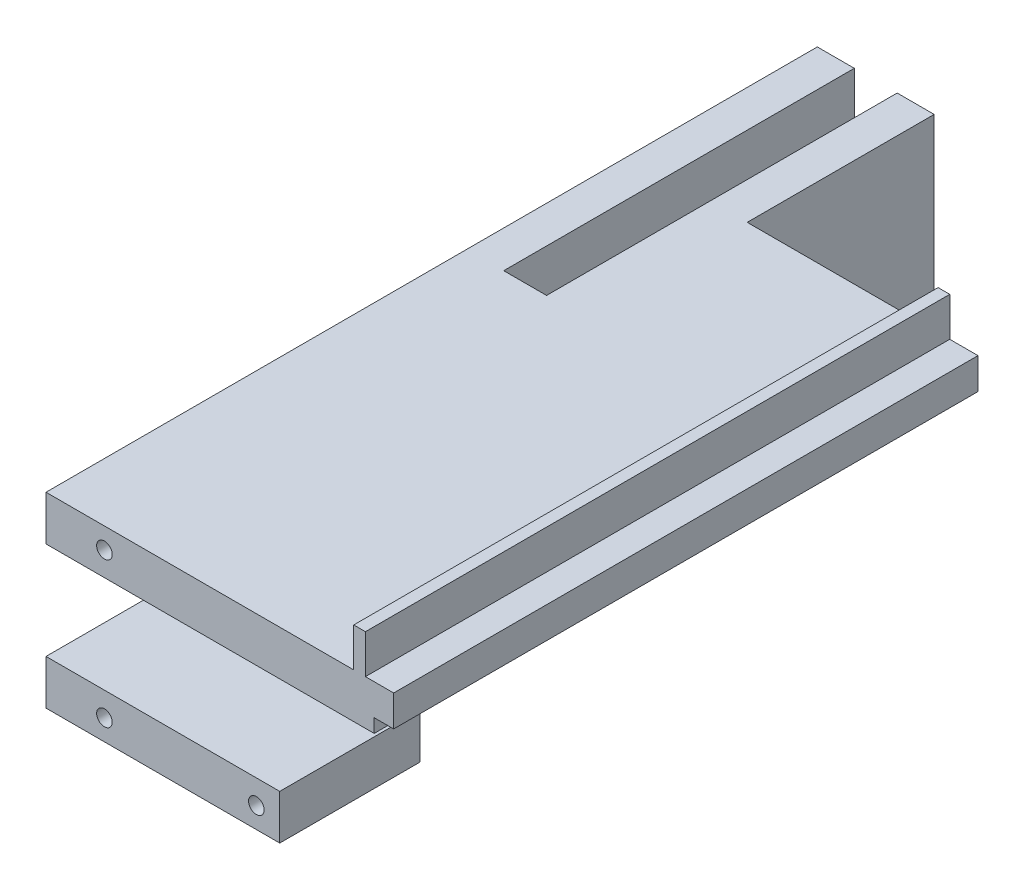
SolidWorks part; units mm, degrees
ref_plane "Alzado" through (0, 0, 0) normal (0, 0, 1) x (1, 0, 0)
ref_plane "Planta" through (0, 0, 0) normal (0, 1, 0) x (1, 0, 0)
ref_plane "Vista lateral" through (0, 0, 0) normal (1, 0, 0) x (0, 0, -1)
sketch "Croquis1" plane through (0, 0, 0) normal (0, 0, 1) x (1, 0, 0)
  line L1 (-66.2162, 31.0113) -> (-6.2162, 31.0113)
  line L2 (-66.2162, 31.0113) -> (-66.2162, -16.9887)
  line L3 (-66.2162, -16.9887) -> (-6.2162, -16.9887)
  line L4 (-6.2162, 31.0113) -> (-6.2162, -16.9887)
  dimension "D1" = 48
  dimension "D2" = 60
extrude "Saliente-Extruir1" add sketch "Croquis1" along normal blind 6
sketch "Croquis4" plane through (0, 0, 6) normal (0, 0, 1) x (1, 0, 0)
  line L0 (-66.2162, 31.0113) -> (-66.2162, 19.5113)
  line L1 (-66.2162, 31.0113) -> (-66.2162, -16.9887) construction
  line L3 (-66.2162, -5.4887) -> (-66.2162, -16.9887)
  line L4 (-66.2162, 31.0113) -> (-6.2162, 31.0113)
  line L6 (-6.2162, 31.0113) -> (-6.2162, 19.5113)
  line L7 (-6.2162, -16.9887) -> (-6.2162, 31.0113) construction
  line L8 (-6.2162, 19.5113) -> (-66.2162, 19.5113)
  line L9 (-66.2162, -5.4887) -> (-6.2162, -5.4887)
  line L10 (-6.2162, -5.4887) -> (-6.2162, -16.9887)
  line L11 (-6.2162, -16.9887) -> (-66.2162, -16.9887)
  dimension "D1" = 25
extrude "Saliente-Extruir3" add sketch "Croquis4" along normal blind 30
sketch "Croquis3" plane through (0, 0, 6) normal (0, 0, 1) x (1, 0, 0)
  circle A0 centre (-51.2162, 25.6613) radius 2.125
  circle A1 centre (-12.2162, 25.6613) radius 2.125
  circle A2 centre (-12.2162, -11.6387) radius 2.125
  circle A3 centre (-51.2162, -11.6387) radius 2.125
  dimension "D7" = 4.25
  dimension "D9" = 4.25
  dimension "D10" = 4.25
  dimension "D2" = 4.25
  dimension "D3" = 37.3
  dimension "D4" = 39
sketch "Croquis5" plane through (0, 0, 36) normal (0, 0, 1) x (1, 0, 0)
  circle A0 centre (-51.2162, 25.6613) radius 2
  circle A1 centre (-12.2162, 25.6613) radius 2
  circle A2 centre (-12.2162, -11.6387) radius 2
  circle A3 centre (-51.2162, -11.6387) radius 2
  dimension "D1" = 4
  dimension "D2" = 4
  dimension "D3" = 4
  dimension "D4" = 4
extrude "Cortar-Extruir3" cut sketch "Croquis5" against normal blind 16
sketch "Croquis6" plane through (0, 0, 0) normal (0, 0, -1) x (-1, 0, 0)
  line L0 (66.2162, -16.9887) -> (6.2162, -16.9887) construction
  line L1 (66.2162, 31.0113) -> (36.2162, 31.0113)
  line L2 (66.2162, 31.0113) -> (66.2162, -16.9887)
  line L3 (66.2162, -16.9887) -> (36.2162, -16.9887)
  line L4 (36.2162, 31.0113) -> (36.2162, -16.9887)
  dimension "D1" = 30
extrude "Saliente-Extruir4" add sketch "Croquis6" along normal blind 162
sketch "Croquis7" plane through (0, 0, -162) normal (0, 0, -1) x (-1, 0, 0)
  circle A0 centre (51.2162, 7.0113) radius 2
  dimension "D1" = 4
extrude "Cortar-Extruir4" cut sketch "Croquis7" against normal blind 16
sketch "Croquis8" plane through (0, 0, -162) normal (0, 0, -1) x (-1, 0, 0)
  line L0 (41.2162, 12.0113) -> (41.2162, 9.5131)
  line L10 (36.2162, 12.0113) -> (41.2162, 12.0113)
  line L11 (36.2162, 12.0113) -> (36.2162, 2.0113)
  line L12 (36.2162, 2.0113) -> (41.2162, 2.0113)
  line L21 (41.2162, 9.5131) -> (44.2162, 9.5131)
  line L23 (41.2162, 4.5131) -> (44.2162, 4.5131)
  line L24 (44.2162, 9.5131) -> (44.2162, 4.5131)
  line L25 (41.2162, 2.0113) -> (41.2162, 4.5131)
  dimension "D1" = 5
  dimension "D2" = 3
  dimension "D3" = 5
sketch "Croquis11" plane through (-36.2162, 0, 0) normal (1, 0, 0) x (0, 0, -1)
  line L1 (-36, 19.5113) -> (-36, 31.0113) construction
  line L4 (-36, 19.5113) -> (-36, 31.0113)
  line L6 (-36, 19.5113) -> (114, 19.5113)
  line L7 (114, 19.5113) -> (114, 31.0113)
  line L8 (162, 31.0113) -> (0, 31.0113) construction
  line L9 (162, 31.0113) -> (0, 31.0113) construction
  line L10 (-36, 31.0113) -> (114, 31.0113)
  dimension "D1" = 150
extrude "Saliente-Extruir6" add sketch "Croquis11" along normal blind 59.25
sketch "Croquis12" plane through (0, 31.0113, 0) normal (0, 1, 0) x (1, 0, 0)
  line L0 (23.0338, -36) -> (-66.2162, -36) construction
  line L1 (15.7838, -36) -> (12.7838, -36)
  line L2 (-66.2162, -36) -> (-66.2162, 162) construction
  line L3 (-66.2162, -36) -> (-66.2162, 162) construction
  line L4 (15.7838, -36) -> (15.7838, 114)
  line L5 (15.7838, 114) -> (12.7838, 114)
  line L6 (23.0338, 114) -> (-36.2162, 114) construction
  line L7 (12.7838, 114) -> (12.7838, -36)
  dimension "D1" = 82
  dimension "D2" = 150
  dimension "D3" = 3
extrude "Saliente-Extruir7" add sketch "Croquis12" along normal blind 10
sketch "Croquis14" plane through (0, 0, -114) normal (0, 0, -1) x (-1, 0, 0)
  line L0 (-23.0338, 23.0113) -> (-18.0338, 23.0113)
  line L1 (-18.0338, 23.0113) -> (-18.0338, 19.5113)
  line L2 (-23.0338, 23.0113) -> (-23.0338, 19.5113)
  line L3 (-23.0338, 19.5113) -> (-18.0338, 19.5113)
  line L4 (36.2162, 19.5113) -> (36.2162, 31.0113)
  line L5 (36.2162, 31.0113) -> (-12.7838, 31.0113)
  line L6 (-23.0338, 31.0113) -> (-23.0338, 19.5113)
  line L7 (-23.0338, 19.5113) -> (36.2162, 19.5113)
  line L8 (36.2162, 19.5113) -> (36.2162, 31.0113) construction
  line L9 (36.2162, 31.0113) -> (-12.7838, 31.0113) construction
  line L10 (-23.0338, 31.0113) -> (-23.0338, 19.5113) construction
  line L11 (-23.0338, 19.5113) -> (36.2162, 19.5113) construction
  line L20 (-12.7838, 31.0113) -> (-12.7838, 41.0113)
  line L22 (-12.7838, 41.0113) -> (-15.7838, 41.0113)
  line L24 (-15.7838, 41.0113) -> (-15.7838, 31.0113)
  line L26 (-15.7838, 31.0113) -> (-23.0338, 31.0113)
  line L27 (-15.7838, 31.0113) -> (-23.0338, 31.0113) construction
  dimension "D2" = 5
  dimension "D3" = 8
  dimension "D1" = 0
extrude "Cortar-Extruir6" cut sketch "Croquis14" against normal through all both and the other way through all
sketch "Croquis15" plane through (0, 0, -162) normal (0, 0, -1) x (-1, 0, 0)
  line L0 (51.2162, 45.0729) -> (51.2162, 16.9496) construction
  line L1 (56.7162, 20.0113) -> (45.7162, 20.0113)
  line L2 (45.7162, 20.0113) -> (45.7162, 31.0113)
  line L3 (56.7162, 20.0113) -> (56.7162, 31.0113)
  line L4 (66.2162, -16.9887) -> (66.2162, 31.0113)
  line L5 (66.2162, 31.0113) -> (36.2162, 31.0113)
  line L6 (36.2162, 31.0113) -> (36.2162, -16.9887)
  line L7 (36.2162, -16.9887) -> (66.2162, -16.9887)
  line L8 (66.2162, -16.9887) -> (66.2162, 31.0113) construction
  line L9 (66.2162, 31.0113) -> (36.2162, 31.0113) construction
  line L10 (56.7162, 31.0113) -> (45.7162, 31.0113)
  point P6 (51.2162, 31.0113)
  point P10 (51.2162, 20.0113)
  dimension "D2" = 11
  dimension "D3" = 11
  dimension "D1" = 0
extrude "Cortar-Extruir7" cut sketch "Croquis15" against normal blind 90 and the other way through all
